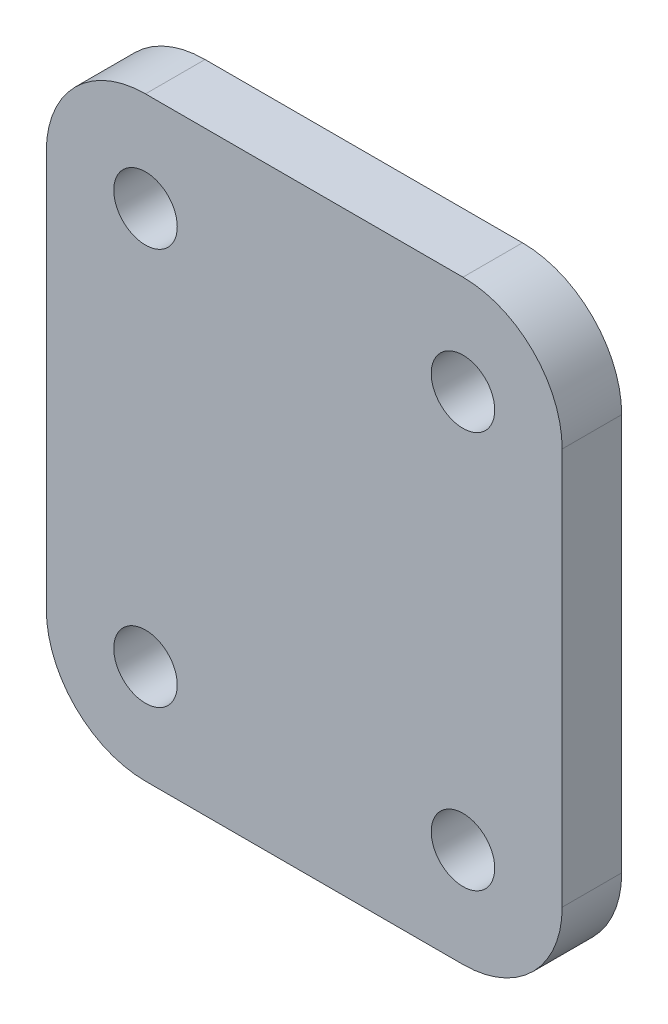
SolidWorks part; units mm, degrees
ref_plane "Plano frontal" through (0, 0, 0) normal (0, 0, 1) x (1, 0, 0)
ref_plane "Plano superior" through (0, 0, 0) normal (0, 1, 0) x (1, 0, 0)
ref_plane "Plano direito" through (0, 0, 0) normal (1, 0, 0) x (0, 0, -1)
sketch "Esboço1" plane through (0, 0, 0) normal (0, 0, 1) x (1, 0, 0)
  line L1 (-13, -15) -> (13, -15)
  line L2 (-13, -15) -> (-13, 15)
  line L3 (-13, 15) -> (13, 15)
  line L4 (13, -15) -> (13, 15)
  line L5 (0, 15) -> (0, -15) construction
  line L6 (-13, 0) -> (13, 0) construction
  circle A0 centre (-8, 10) radius 1.6
  circle A2 centre (8, 10) radius 1.6
  circle A3 centre (8, -10) radius 1.6
  circle A4 centre (-8, -10) radius 1.6
  circle A5 centre (0, 0) radius 3.5 construction
  point P0 (0, 0)
  dimension "D1" = 16
  dimension "D2" = 20
  dimension "D3" = 5
  dimension "D5" = 3.2
  dimension "D6" = 7
  dimension "D4" = 5
extrude "Ressalto-extrusão1" add sketch "Esboço1" along normal blind 3 contours L1 L4 L3 L2 A5 A2 A0 A3 A4 region at (0, 0, 0)
fillet "Filete1" radius 5 4 edges at (-13, -15, 1.5) (13, -15, 1.5) (-13, 15, 1.5) (13, 15, 1.5)
